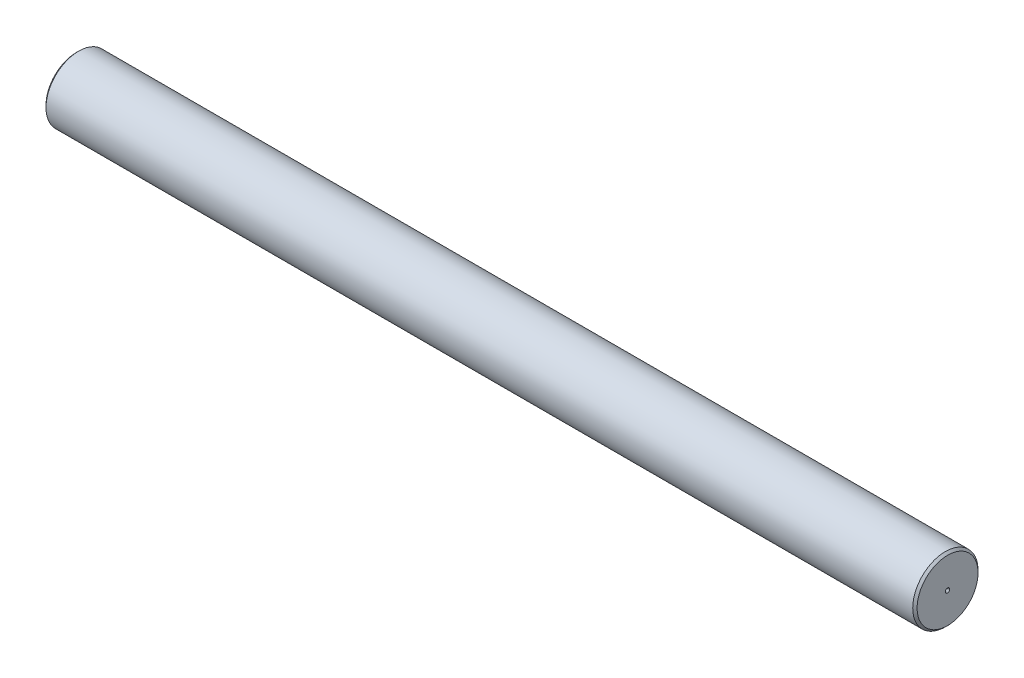
SolidWorks part; units mm, degrees
ref_plane "Front Plane" through (0, 0, 0) normal (0, 0, 1) x (1, 0, 0)
ref_plane "Top Plane" through (0, 0, 0) normal (0, 1, 0) x (1, 0, 0)
ref_plane "Right Plane" through (0, 0, 0) normal (1, 0, 0) x (0, 0, -1)
sketch "Sketch1" plane through (0, 0, 0) normal (0, 0, 1) x (1, 0, 0)
  line L0 (0, 0) -> (200, 0) construction
  line L2 (0, 7.5) -> (200, 7.5)
  line L3 (0, 7.5) -> (0, 0)
  line L4 (0, 0) -> (200, 0)
  line L5 (200, 7.5) -> (200, 0)
  dimension "L" = 200
  dimension "D_s" = 15
revolve "Revolve1" add sketch "Sketch1" angle 360 about L0
sketch "Sketch2" plane through (0, 0, 0) normal (0, 0, 1) x (1, 0, 0)
  line L0 (0, 0) -> (200, 0) construction
  line L1 (200, -7.5) -> (200, 7.5) construction
  line L2 (0, 0.5) -> (0, 0)
  line L3 (0, 0) -> (0.5, 0)
  line L4 (0, 0.5) -> (0.5, 0)
  line L5 (199.5, 0) -> (200, 0.5)
  line L6 (199.5, 0) -> (200, 0)
  line L7 (200, 0.5) -> (200, 0)
  line L8 (0, 7.5) -> (0, -7.5) construction
  dimension "D1" = 1
  dimension "D2" = 0.5
revolve "Cut-Revolve1" cut sketch "Sketch2" angle 360 about L0
chamfer "Chamfer1" distance 0.5 angle 45 2 edges at (200, 0, 7.5) (0, 0, 7.5)
